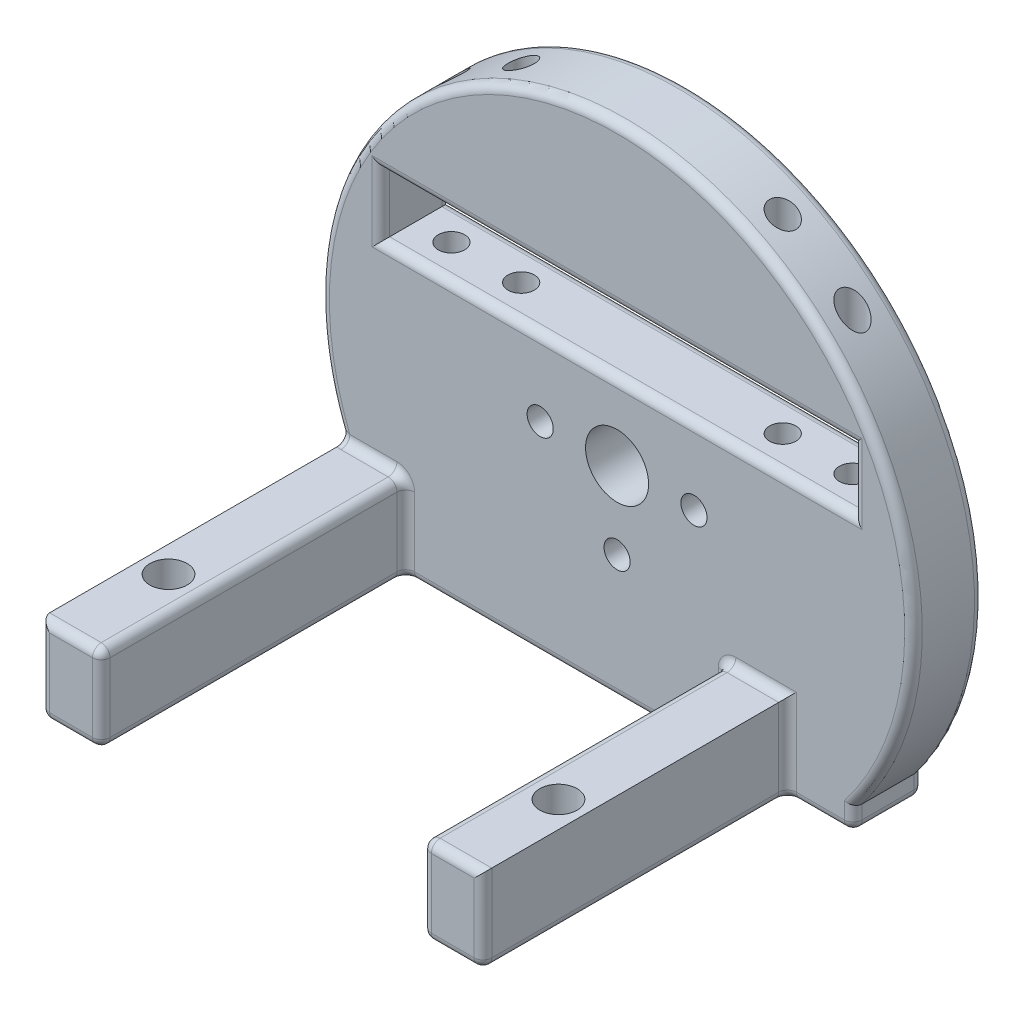
SolidWorks part; units mm, degrees
ref_plane "Front Plane" through (0, 0, 0) normal (0, 0, 1) x (1, 0, 0)
ref_plane "Top Plane" through (0, 0, 0) normal (0, 1, 0) x (1, 0, 0)
ref_plane "Right Plane" through (0, 0, 0) normal (1, 0, 0) x (0, 0, -1)
sketch "Sketch1" plane through (0, 0, 0) normal (0, 0, 1) x (1, 0, 0)
  line L0 (0, 0) -> (7, 0) construction
  line L1 (0, 0) -> (0, -7) construction
  line L2 (-23.9975, -18.37) -> (14.7775, -18.37)
  line L3 (14.7775, -18.37) -> (14.7775, 6.91)
  line L4 (14.7775, 6.91) -> (-23.9975, 6.91)
  line L5 (-23.9975, 6.91) -> (-23.9975, -18.37)
  circle A0 centre (0, 0) radius 2.8702
  circle A1 centre (0, -7) radius 1.1906
  circle A2 centre (7, 0) radius 1.1906
  circle A5 centre (-7, 0) radius 1.1906
  circle A6 centre (0, -7) radius 1.1906 [skipped]
  dimension "D1" = 5.7404
  dimension "D2" = 2.3813
  dimension "D4" = 90
  dimension "D5" = 7
  dimension "D6" = 7
  dimension "D7" = 18.37
  dimension "D8" = 7.7775
  dimension "D9" = 6.91
  dimension "D10" = 16.9975
  dimension "D3" = 3
extrude "Boss-Extrude1" add sketch "Sketch1" along normal blind 6.35
sketch "Sketch4" plane through (0, 0, 6.35) normal (0, 0, 1) x (1, 0, 0)
  line L0 (14.7775, -18.37) -> (10.015, -18.37)
  line L1 (-23.9975, -18.37) -> (14.7775, -18.37) construction
  line L2 (10.015, -18.37) -> (10.015, -10.49)
  line L3 (10.015, -10.49) -> (14.7775, -10.49)
  line L4 (14.7775, -18.37) -> (14.7775, 6.91) construction
  line L5 (14.7775, -10.49) -> (14.7775, -18.37) construction
  line L6 (-23.9975, -18.37) -> (-23.9975, -10.49) construction
  line L7 (-23.9975, 6.91) -> (-23.9975, -18.37) construction
  line L8 (-23.9975, -10.49) -> (-19.235, -10.49)
  line L9 (-19.235, -10.49) -> (-19.235, -18.37)
  line L10 (-19.235, -18.37) -> (-23.9975, -18.37)
  line L11 (-4.61, -18.37) -> (-4.61, 6.91) construction
  line L12 (14.7775, 6.91) -> (-23.9975, 6.91) construction
  line L13 (-23.9975, -10.49) -> (-24.735, -10.49)
  line L14 (-24.735, -10.49) -> (-24.735, -18.37)
  line L15 (-24.735, -18.37) -> (-23.9975, -18.37)
  line L16 (14.7775, -18.37) -> (15.515, -18.37)
  line L17 (15.515, -18.37) -> (15.515, -10.49)
  line L18 (15.515, -10.49) -> (14.7775, -10.49)
  dimension "D1" = 7.88
  dimension "D2" = 4.7625
  dimension "D3" = 5.5
  dimension "D4" = 5.5
extrude "Boss-Extrude3" add sketch "Sketch4" along normal blind 27.7206
sketch "Sketch6" plane through (-23.9975, 0, 0) normal (-1, 0, 0) x (0, 0, 1)
  line L5 (0, 6.91) -> (0, -18.37)
  line L6 (0, -18.37) -> (6.35, -18.37)
  line L7 (6.35, -18.37) -> (6.35, -10.49)
  line L8 (6.35, -10.49) -> (6.35, 6.91)
  line L9 (6.35, 6.91) -> (0, 6.91)
  line L10 (0, 6.91) -> (0, -18.37)
  line L11 (0, -18.37) -> (6.35, -18.37)
  line L12 (6.35, -18.37) -> (6.35, -10.49)
  line L13 (6.35, -10.49) -> (6.35, 6.91)
  line L14 (6.35, 6.91) -> (0, 6.91)
  dimension "D1" = 0
extrude "Boss-Extrude4" add sketch "Sketch6" along normal up to surface (0.7375 mm away) up to face at (-24.735, -14.43, 20.2103)
sketch "Sketch2" plane through (0, 0, 6.35) normal (0, 0, 1) x (1, 0, 0)
  line L0 (0, 0) -> (-24.735, -10.7937) construction
  line L1 (0, 0) -> (21.5, -16.3118) construction
  line L2 (0, 0) -> (0, -5.3434) construction
  line L4 (-21.5, 6.91) -> (-21.5, 12.51)
  line L5 (14.7775, 6.91) -> (-24.735, 6.91) construction
  line L6 (-21.5, 12.51) -> (21.5, 12.51)
  line L7 (21.5, 12.51) -> (21.5, 6.91)
  line L8 (21.5, 6.91) -> (-21.5, 6.91)
  line L9 (21.5, -16.3118) -> (14.7775, -16.3118)
  line L10 (14.7775, -10.49) -> (14.7775, 6.91) construction
  line L11 (14.7775, -16.3118) -> (14.7775, 6.91)
  line L12 (-24.735, -10.7937) -> (-24.735, 6.91)
  line L13 (-24.735, 6.91) -> (-21.5, 6.91)
  line L14 (14.7775, 6.91) -> (-21.5, 6.91)
  line L15 (21.5, -16.3118) -> (21.5, -18.37)
  line L26 (-24.735, 6.91) -> (-24.735, -10.49) construction
  line L32 (21.5, -18.37) -> (14.7775, -18.37)
  line L33 (14.7775, -18.37) -> (14.7775, -16.3118)
  line L34 (21.5, -16.3118) -> (14.7775, -16.3118)
  circle A0 centre (0, 0) radius 2.8702 construction
  circle A1 centre (0, 0) radius 2.8702 construction
  arc A2 (-24.735, -10.7937) -> (21.5, -16.3118) centre (0, 0) cw
  circle A3 centre (7, 0) radius 1.1906 construction
  circle A4 centre (7, 0) radius 1.1906 construction
  line M31 (14.7775, -10.49) -> (14.7775, 6.91)
  line M32 (14.7775, 6.91) -> (-24.735, 6.91)
  dimension "D3" = 26.9875
  dimension "D1" = 5.6
  dimension "D2" = 43
  dimension "D4" = 5.3434
extrude "Boss-Extrude2" add sketch "Sketch2" against normal up to surface (6.35 mm away) contours A2 L4 L6 L7 L8 L9 M32 M31 | L32 L15 L9 M31 region at (-23.1175, 7.602, 6.35) region at (18.1387, -17.3409, 6.35) up to face at (-4.9788, -5.73, 0)
sketch "Sketch3" plane through (0, 6.91, 0) normal (0, 1, 0) x (1, 0, 0)
  line L0 (0, 0) -> (0, -6.35) construction
  line L1 (21.5, 0) -> (-21.5, 0) construction
  line L2 (21.5, -6.35) -> (-21.5, -6.35) construction
  circle A0 centre (18.2563, -3.175) radius 1.2
  circle A1 centre (11.9062, -3.175) radius 1.2
  circle A2 centre (-18.2563, -3.175) radius 1.2
  circle A3 centre (-11.9062, -3.175) radius 1.2
  point P19 (0, -3.175)
  dimension "D1" = 2.4
  dimension "D2" = 6.35
  dimension "D3" = 6.35
  dimension "D4" = 23.8125
extrude "Cut-Extrude1" cut sketch "Sketch3" against normal through all both and the other way through all
sketch "Sketch5" plane through (0, -10.49, 0) normal (0, 1, 0) x (1, 0, 0)
  line L1 (-19.235, -6.35) -> (10.015, -6.35) construction
  line L2 (-19.235, -6.35) -> (10.015, -6.35) construction
  line L3 (-4.61, -6.35) -> (-4.61, -23.4269) construction
  line L8 (15.515, -34.0706) -> (10.015, -34.0706) construction
  line L9 (10.015, -34.0706) -> (10.015, -6.35) construction
  arc A0 (13.14, -23.125) -> (13.14, -26.525) centre (13.14, -24.825) ccw construction
  arc A1 (-22.36, -23.125) -> (-22.36, -26.525) centre (-22.36, -24.825) cw construction
  circle A2 centre (13.14, -24.825) radius 1.7
  circle A3 centre (-22.36, -24.825) radius 1.7
  dimension "D3" = 1.7
  dimension "D1" = 17.0769
  dimension "D2" = 9.2456
  dimension "D4" = 3.125
extrude "Cut-Extrude2" cut sketch "Sketch5" against normal up to surface (7.88 mm away) up to face at (17.0563, -18.37, 3.175)
fillet "Fillet1" radius 0.8 13 edges at (21.5, 9.71, 6.35) (21.5, 9.71, 0) (0, 6.91, 6.35) (0, 6.91, 0) (-21.5, 9.71, 6.35) (-21.5, 9.71, 0) (0, 12.51, 6.35) (0, 12.51, 0) (21.5, -17.3409, 0) (21.5, -17.3409, 6.35) (3.1982, 26.7973, 0) (3.1982, 26.7973, 6.35) (-24.735, -14.5819, 0)
fillet "Fillet2" radius 0.8 27 edges at (18.1075, -18.37, 6.35) (21.2657, -18.37, 6.1157) (21.5, -18.37, 3.175) (21.2657, -18.37, 0.2343) (-1.6175, -18.37, 0) (-4.61, -18.37, 6.35) (12.765, -18.37, 34.0706) (12.765, -10.49, 34.0706) (10.015, -14.43, 34.0706) (10.015, -18.37, 20.2103) (10.015, -10.49, 20.2103) (-19.235, -18.37, 20.2103) (-21.985, -18.37, 34.0706) (-21.985, -10.49, 34.0706) (-19.235, -14.43, 34.0706) (-19.235, -10.49, 20.2103) (-24.3037, -10.49, 6.2981) (-21.6148, -10.49, 6.35) (-24.5007, -18.37, 0.2343) (-24.735, -14.43, 34.0706) (15.515, -14.43, 34.0706) (15.515, -14.43, 6.35) (-19.235, -14.43, 6.35) (15.515, -18.37, 20.2103) (-24.735, -18.37, 17.4353) (10.015, -14.43, 6.35) (12.765, -10.49, 6.35) tangent propagation no
